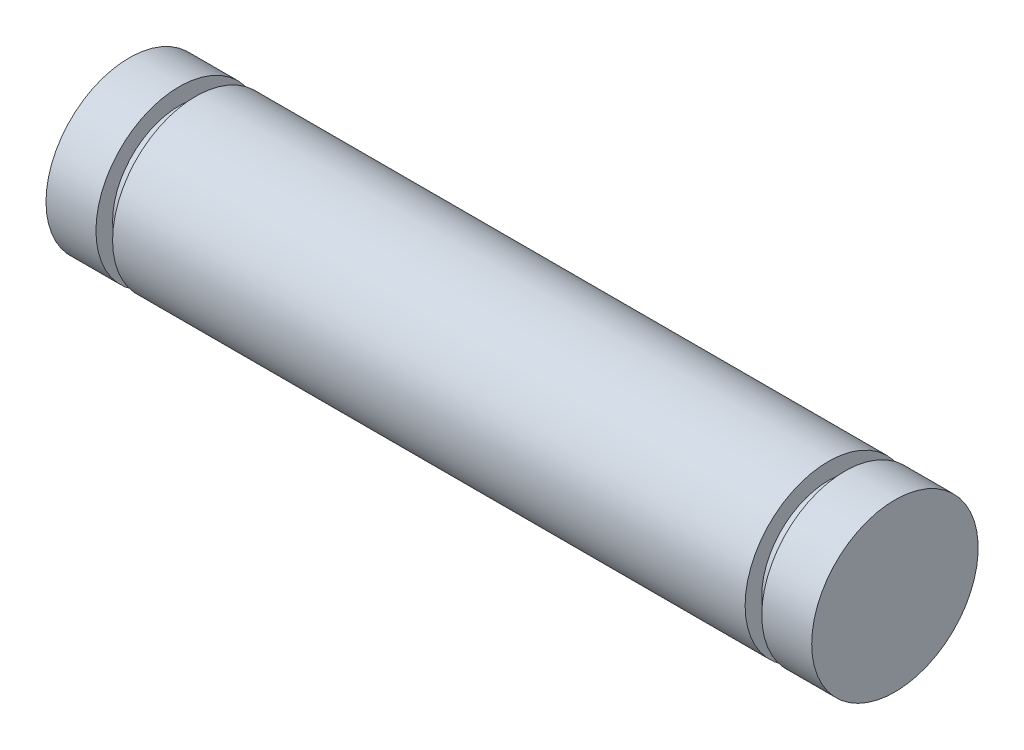
SolidWorks part; units mm, degrees
ref_plane "正面" through (0, 0, 0) normal (0, 0, 1) x (1, 0, 0)
ref_plane "平面" through (0, 0, 0) normal (0, 1, 0) x (1, 0, 0)
ref_plane "右側面" through (0, 0, 0) normal (1, 0, 0) x (0, 0, -1)
sketch "ｽｹｯﾁ1" plane through (0, 0, 0) normal (0, 0, 1) x (1, 0, 0)
  line L0 (0, 0) -> (23, 0) construction
  line L1 (0, 0) -> (0, 5)
  line L2 (0, 5) -> (19, 5)
  line L3 (19, 5) -> (19, 4)
  line L4 (19, 4) -> (20, 4)
  line L5 (20, 4) -> (20, 5)
  line L6 (20, 5) -> (23, 5)
  line L7 (23, 5) -> (23, 0)
  line L8 (0, 0) -> (23, 0)
  dimension "D1" = 1
  dimension "D2" = 3
  dimension "D3" = 5
  dimension "D4" = 19
revolve "回転1" add sketch "ｽｹｯﾁ1" angle 360 about L0
mirror "ﾐﾗｰ1" about plane through (0, 0, 0) normal (1, 0, 0) of bodies 105
